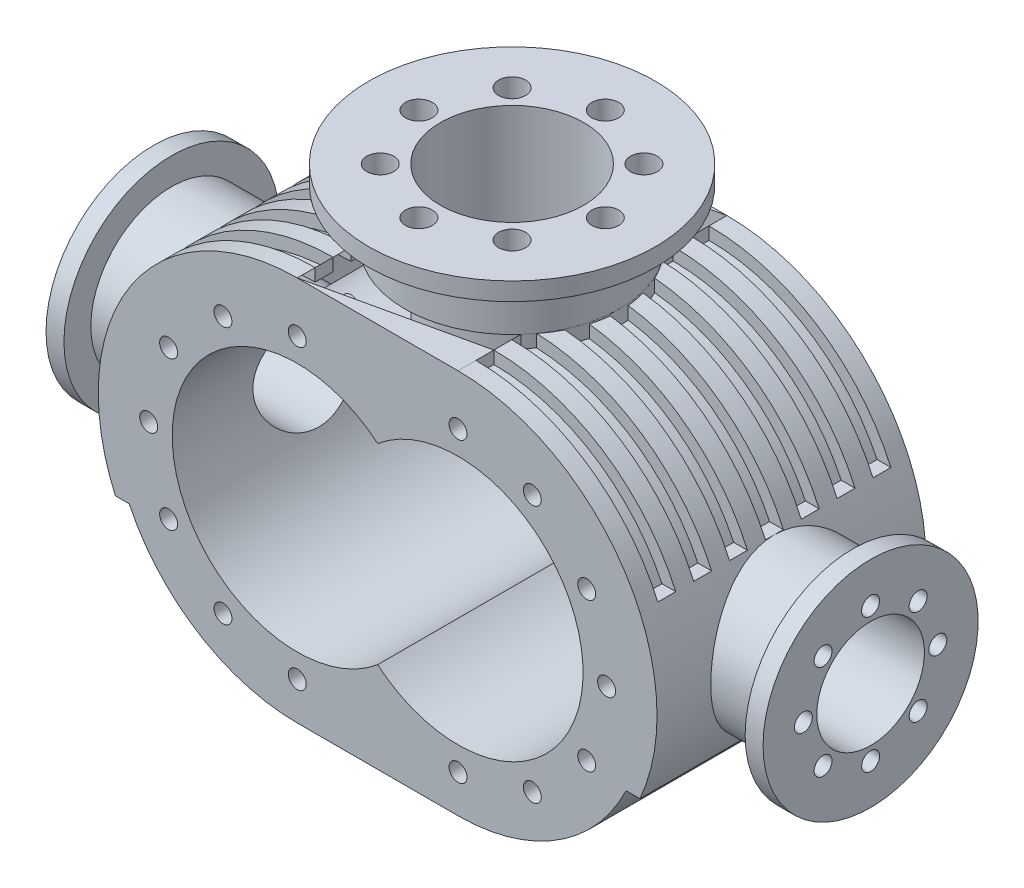
SolidWorks part; units mm, degrees
note: The reader was unsure of these and kept them because the rebuilt part matched: shared geometry of "Çizim1<5>", "Çizim1<6>", "Çizim1<7>", "Çizim1<9>", "Çizim1<10>".
ref_plane "Ön Düzlem" through (0, 0, 0) normal (0, 0, 1) x (1, 0, 0)
ref_plane "Üst Düzlem" through (0, 0, 0) normal (0, 1, 0) x (1, 0, 0)
ref_plane "Sağ Düzlem" through (0, 0, 0) normal (1, 0, 0) x (0, 0, -1)
sketch "Çizim1" plane through (0, 0, 0) normal (0, 0, 1) x (1, 0, 0)
  line L0 (0, 159.5985) -> (0, -159.5985) construction
  line L1 (-44.845, 202.9428) -> (-44.845, -202.9428) construction
  line L2 (44.845, 196.9387) -> (44.845, -196.9387) construction
  line L3 (0, 0) -> (200, 0) construction
  line L4 (200, 60) -> (200, -60)
  line L5 (200, 60) -> (190, 60)
  line L6 (190, 60) -> (190, 45)
  line L7 (190, 45) -> (146.3142, 45)
  line L8 (190, -45) -> (146.3142, -45)
  line L9 (190, -60) -> (190, -45)
  line L10 (200, -60) -> (190, -60)
  line L11 (-200, 60) -> (-190, 60)
  line L12 (-190, 60) -> (-190, 45)
  line L13 (-190, 45) -> (-146.3142, 45)
  line L14 (-190, -45) -> (-146.3142, -45)
  line L15 (-190, -60) -> (-190, -45)
  line L16 (-200, -60) -> (-190, -60)
  line L17 (-200, 60) -> (-200, -60)
  line L18 (-44.845, -111) -> (44.845, -111)
  line L19 (-44.845, 111) -> (44.845, 111)
  line L20 (-200, 0) -> (-155.845, 0)
  line L21 (155.845, 0) -> (200, 0)
  line L23 (-59.991, 109.9618) -> (-59.991, 141.0001)
  line L24 (-59.991, 141.0001) -> (-79.991, 141.0001)
  line L25 (-79.991, 141.0001) -> (-79.991, 151.0001)
  line L26 (-79.991, 151.0001) -> (0, 151.0001)
  line L27 (0, 151.0001) -> (0, 111)
  line L28 (44.845, 104) -> (44.845, 111)
  line L29 (-44.845, 111) -> (-44.845, 104)
  line L30 (44.845, 111) -> (44.845, 104)
  line L31 (44.845, -104) -> (44.845, -111)
  line L32 (-44.845, -104) -> (-44.845, -111)
  line L33 (-44.845, -104) -> (44.845, -104)
  circle A1 centre (-44.845, 0) radius 10
  circle A2 centre (44.845, 0) radius 10
  arc A3 (0, 53.4227) -> (0, -53.4227) centre (-44.845, 0) ccw
  arc A4 (0, -53.4227) -> (0, 53.4227) centre (44.845, 0) ccw
  arc A6 (-44.845, 111) -> (-44.845, -111) centre (-44.845, 0) ccw
  arc A9 (-44.845, 104) -> (-44.845, -104) centre (-44.845, 0) ccw
  arc A10 (44.845, -111) -> (44.845, 111) centre (44.845, 0) ccw
  arc A11 (44.845, -104) -> (44.845, 104) centre (44.845, 0) ccw
  point P4 (0, 0)
  point P10 (-44.845, 0)
  point P15 (44.845, 0)
  point P25 (200, 0)
  dimension "D6" = 139.5
  dimension "D1" = 20
  dimension "D2" = 20
  dimension "D5" = 139.5
  dimension "D3" = 222
  dimension "D7" = 200
  dimension "D8" = 111
  dimension "D16" = 208
  dimension "D17" = 208
  dimension "D4" = 44.845
  dimension "D9" = 120
  dimension "D10" = 10
  dimension "D11" = 15
  dimension "D12" = 60
  dimension "D13" = 31.0383
  dimension "D14" = 20
  dimension "D15" = 10
extrude "Yükseklik-Ekstrüzyon1" add sketch "Çizim1" along normal mid plane 150 contours A10 L19 A6 L18 A4 A3
revolve "Döndür2" add sketch "Çizim1<5>" angle 360 about L3
sketch "Çizim1<5>" plane through (0, 0, 0) normal (0, 0, 1) x (1, 0, 0) same geometry as "Çizim1"
revolve "Döndür3" add sketch "Çizim1<6>" angle 360 about L3
sketch "Çizim1<6>" plane through (0, 0, 0) normal (0, 0, 1) x (1, 0, 0) same geometry as "Çizim1"
revolve "Döndür4" add sketch "Çizim1<7>" angle 360 about L0
sketch "Çizim1<7>" plane through (0, 0, 0) normal (0, 0, 1) x (1, 0, 0) same geometry as "Çizim1"
extrude "Yükseklik-Ekstrüzyon2" add sketch "Çizim1<9>" along normal mid plane 150 contours L33 A11 L28 L19 L29 A9 A4 A3
sketch "Çizim1<9>" plane through (0, 0, 0) normal (0, 0, 1) x (1, 0, 0) same geometry as "Çizim1"
extrude "Yükseklik-Ekstrüzyon3" add sketch "Çizim1<10>" along normal mid plane 150 contours A11 L31 A10 L28 | L33 L32 L18 L31
sketch "Çizim1<10>" plane through (0, 0, 0) normal (0, 0, 1) x (1, 0, 0) same geometry as "Çizim1"
sketch "Çizim3" plane through (0, 0, 75) normal (0, 0, 1) x (1, 0, 0)
  line L0 (-44.845, -111) -> (-44.845, 111) construction
  line L1 (44.845, -111) -> (44.845, 111) construction
  line L2 (0, 0) -> (-200, 0) construction
  line L3 (-200, 0) -> (-200, 45) construction
  line L4 (-200, 45) -> (-146.3142, 45) construction
  line L5 (-146.3142, 45) -> (-138.6053, 45)
  line L6 (-200, 0) -> (-200, -45) construction
  line L7 (-200, -45) -> (-146.3142, -45) construction
  line L8 (-146.3142, -45) -> (-138.6053, -45)
  line L9 (-44.845, -104) -> (-44.845, -111)
  line L10 (-44.845, 104) -> (-44.845, 111)
  line L11 (44.845, 104) -> (44.845, 111)
  line L12 (44.845, -104) -> (44.845, -111)
  line L13 (-44.845, -104) -> (44.845, -104)
  line L14 (-44.845, -111) -> (44.845, -111)
  line L15 (0, 0) -> (200, 0) construction
  line L16 (200, -45) -> (200, 45) construction
  line L17 (200, 45) -> (146.3142, 45) construction
  line L18 (200, -45) -> (146.3142, -45) construction
  line L19 (146.3142, 45) -> (138.6053, 45)
  line L20 (146.3142, -45) -> (138.6053, -45)
  arc A0 (-44.845, 104) -> (-44.845, -104) centre (-44.845, 0) ccw
  arc A1 (-44.845, 111) -> (-44.845, -111) centre (-44.845, 0) ccw
  arc A6 (44.845, -111) -> (44.845, 111) centre (44.845, 0) ccw
  arc A7 (44.845, -104) -> (44.845, 104) centre (44.845, 0) ccw
  point P7 (-44.845, 0)
  point P17 (44.845, 0)
  point P29 (200, 0)
  arc M1 (-44.845, 111) -> (-44.845, -111) centre (-44.845, 0) ccw
  line M2 (-44.845, -111) -> (44.845, -111)
  arc M3 (44.845, -111) -> (44.845, 111) centre (44.845, 0) ccw
  dimension "D1" = 208
  dimension "D2" = 222
  dimension "D3" = 104
  dimension "D4" = 200
  dimension "D5" = 45
  dimension "D6" = 45
  dimension "D7" = 200
  dimension "D8" = 90
extrude "Kes-Ekstrüzyon4" cut sketch "Çizim3" against normal through all both and the other way through all contours A0 L10 L5 M1 | A0 L8 L9 M1 | L13 L9 L12 M2 | A7 L12 L20 M3 | A7 L19 L11 M3
ref_plane "Düzlem1" through (0, 111, 0) normal (0, 1, 0) x (1, 0, 0)
sketch "Çizim4" plane through (0, 111, 0) normal (0, 1, 0) x (1, 0, 0)
  circle A0 centre (0, 0) radius 60
  dimension "D1" = 120
extrude "Yükseklik-Ekstrüzyon4" add sketch "Çizim4" against normal up to next
sketch "Çizim5" plane through (0, 151.0001, 0) normal (0, 1, 0) x (1, 0, 0)
  circle A0 centre (0, 0) radius 40
  dimension "D1" = 80
extrude "Kes-Ekstrüzyon5" cut sketch "Çizim5" against normal blind 112
sketch "Çizim6" plane through (-200, 0, 0) normal (-1, 0, 0) x (0, 0, 1)
  circle A0 centre (0, 0) radius 30
  dimension "D1" = 60
extrude "Kes-Ekstrüzyon6" cut sketch "Çizim6" against normal through all
sketch "Çizim7" plane through (0, 0, -75) normal (0, 0, -1) x (-1, 0, 0)
  line L0 (-114.595, 0) -> (-127.72, 0) construction
  line L1 (-44.845, 0) -> (-44.845, 12.0985) construction
  line L2 (0, 0) -> (0, 29.8833) construction
  arc A2 (0, 53.4227) -> (0, -53.4227) centre (-44.845, 0) ccw construction
  circle A3 centre (-127.72, 0) radius 5
  circle A4 centre (-116.6169, -41.4375) radius 5
  circle A5 centre (-86.2825, -71.7719) radius 5
  circle A6 centre (-44.845, -82.875) radius 5
  circle A7 centre (-116.6169, 41.4375) radius 5
  circle A8 centre (-86.2825, 71.7719) radius 5
  circle A9 centre (-44.845, 82.875) radius 5
  circle A10 centre (44.845, -82.875) radius 5
  circle A11 centre (86.2825, -71.7719) radius 5
  circle A12 centre (116.6169, -41.4375) radius 5
  circle A13 centre (127.72, 0) radius 5
  circle A14 centre (116.6169, 41.4375) radius 5
  circle A15 centre (86.2825, 71.7719) radius 5
  circle A16 centre (44.845, 82.875) radius 5
  point P19 (-44.845, 0)
  point P26 (-44.845, 0)
  dimension "D1" = 13.125
  dimension "D2" = 10
  dimension "D4" = 71.7719
  dimension "D3" = 4
  dimension "D5" = 41.4375
  dimension "D6" = 71.7719
  dimension "D7" = 71.7719
  dimension "D8" = 41.4375
  dimension "D9" = 41.4375
  dimension "D10" = 4
extrude "Kes-Ekstrüzyon7" cut sketch "Çizim7" against normal blind 30
mirror "Aynalama1" about plane through (0, 0, 0) normal (0, 0, 1) of "Kes-Ekstrüzyon7"
sketch "Çizim8" plane through (-200, 0, 0) normal (-1, 0, 0) x (0, 0, 1)
  line L0 (0, 0) -> (0, 37.5) construction
  circle A0 centre (0, 37.5) radius 5
  circle A1 centre (26.5165, 26.5165) radius 5
  circle A2 centre (37.5, 0) radius 5
  circle A3 centre (26.5165, -26.5165) radius 5
  circle A4 centre (0, -37.5) radius 5
  circle A5 centre (-26.5165, -26.5165) radius 5
  circle A6 centre (-37.5, 0) radius 5
  circle A7 centre (-26.5165, 26.5165) radius 5
  point P21 (0, 0)
  dimension "D2" = 10
  dimension "D1" = 37.5
  dimension "D3" = 26.5165
  dimension "D4" = 28.7013
extrude "Kes-Ekstrüzyon8" cut sketch "Çizim8" against normal blind 30
mirror "Aynalama2" about plane through (0, 0, 0) normal (1, 0, 0) of "Kes-Ekstrüzyon8"
sketch "Çizim9" plane through (0, 151.0001, 0) normal (0, 1, 0) x (1, 0, 0)
  line L0 (0, 0) -> (52, 0) construction
  circle A0 centre (52, 0) radius 7.5
  circle A1 centre (36.7696, -36.7696) radius 7.5
  circle A2 centre (0, -52) radius 7.5
  circle A3 centre (-36.7696, -36.7696) radius 7.5
  circle A4 centre (-52, 0) radius 7.5
  circle A5 centre (-36.7696, 36.7696) radius 7.5
  circle A6 centre (0, 52) radius 7.5
  circle A7 centre (36.7696, 36.7696) radius 7.5
  point P6 (0, 0)
  point P21 (0, 0)
  dimension "D2" = 15
  dimension "D1" = 52
  dimension "D3" = 36.7696
  dimension "D4" = 36.7696
extrude "Kes-Ekstrüzyon9" cut sketch "Çizim9" against normal blind 40
ref_plane "Düzlem2" through (0, 0, -75) normal (0, 0, 1) x (1, 0, 0)
sketch "Çizim10" plane through (0, 0, -75) normal (0, 0, 1) x (1, 0, 0)
  line L0 (-146.3142, 45) -> (-138.6053, 45)
  line L1 (-44.845, 111) -> (-44.845, 104)
  circle A0 centre (-44.845, 0) radius 111
  circle A1 centre (-44.845, 0) radius 104
  dimension "D1" = 222
  dimension "D2" = 208
extrude "Yükseklik-Ekstrüzyon5" add sketch "Çizim10" along normal blind 10 contours A1 L1 A0 L0
pattern_linear "LÇoğaltma2" count 10 spacing 20 along (0, 0, 1) of "Yükseklik-Ekstrüzyon5"
mirror "Aynalama3" about plane through (0, 0, 0) normal (1, 0, 0) of "LÇoğaltma2", "Yükseklik-Ekstrüzyon5"
